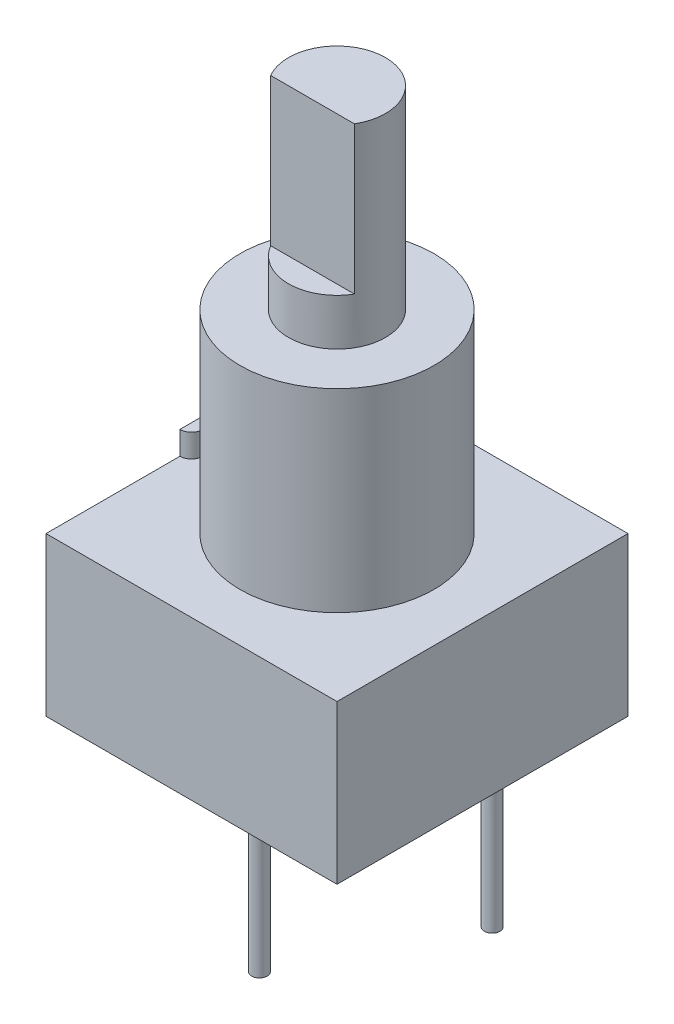
SolidWorks part; units mm, degrees
ref_plane "Front Plane" through (0, 0, 0) normal (0, 0, 1) x (1, 0, 0)
ref_plane "Top Plane" through (0, 0, 0) normal (0, 1, 0) x (1, 0, 0)
ref_plane "Right Plane" through (0, 0, 0) normal (1, 0, 0) x (0, 0, -1)
sketch "Sketch1" plane through (0, 0, 0) normal (0, 1, 0) x (1, 0, 0)
  line L1 (4.7625, -4.7625) -> (-4.7625, -4.7625)
  line L2 (4.7625, -4.7625) -> (4.7625, 4.7625)
  line L3 (4.7625, 4.7625) -> (-4.7625, 4.7625)
  line L4 (-4.7625, -4.7625) -> (-4.7625, 4.7625)
  line L5 (4.7625, -4.7625) -> (-4.7625, 4.7625) construction
  line L6 (4.7625, 4.7625) -> (-4.7625, -4.7625) construction
  point P0 (0, 0)
  dimension "D1" = 9.525
extrude "Boss-Extrude1" add sketch "Sketch1" against normal blind 5.1816
sketch "Sketch2" plane through (0, 0, 0) normal (0, 1, 0) x (1, 0, 0)
  circle A0 centre (0, 0) radius 3.175
  dimension "D1" = 6.35
extrude "Boss-Extrude2" add sketch "Sketch2" along normal blind 6.35
sketch "Sketch3" plane through (0, 0, 0) normal (0, 1, 0) x (1, 0, 0)
  line L0 (-4.7625, 4.7625) -> (-4.7625, -4.7625) construction
  line L1 (-4.7625, 0.381) -> (-4.7625, -0.381)
  arc A0 (-4.7625, -0.381) -> (-4.7625, 0.381) centre (-4.7625, 0) ccw
  dimension "D1" = 0.762
extrude "Boss-Extrude3" add sketch "Sketch3" along normal blind 0.762
sketch "Sketch4" plane through (0, 6.35, 0) normal (0, 1, 0) x (1, 0, 0)
  circle A0 centre (0, 0) radius 1.5875
  dimension "D1" = 3.175
extrude "Boss-Extrude4" add sketch "Sketch4" along normal offset from surface (6.35 mm away) 12.7 contours A0 region at (0, 6.35, 0) up to face at (0, 0, 3.175) offset beyond the face yes
sketch "Sketch5" plane through (0, 12.7, 0) normal (0, 1, 0) x (1, 0, 0)
  line L0 (-1.3711, -0.8001) -> (1.3711, -0.8001)
  circle A1 centre (0, 0) radius 1.5875
  arc A2 (-1.3711, -0.8001) -> (1.3711, -0.8001) centre (0, 0) ccw
  point P5 (0, 1.5875)
  dimension "D2" = 2.3876
  dimension "D1" = 0
extrude "Cut-Extrude1" cut sketch "Sketch5" against normal blind 4.826
sketch "Sketch6" plane through (0, -5.1816, 0) normal (0, -1, 0) x (1, 0, 0)
  circle A0 centre (0, 2.54) radius 0.254
  circle A1 centre (-2.54, -2.54) radius 0.254
  circle A2 centre (2.54, -2.54) radius 0.254
  dimension "D1" = 0.508
  dimension "D4" = 5.08
  dimension "D2" = 2.54
  dimension "D3" = 2.54
  dimension "D5" = 2.54
extrude "Boss-Extrude5" add sketch "Sketch6" along normal blind 5.969
